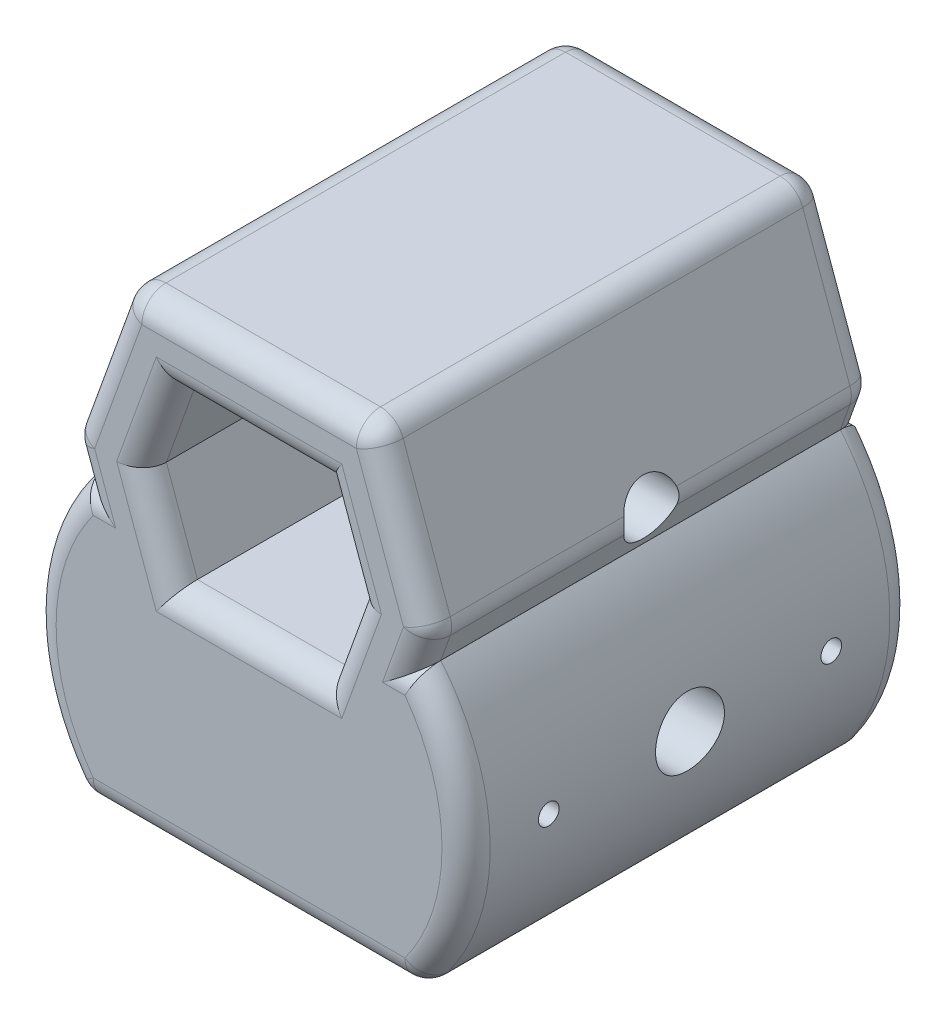
SolidWorks part; units mm, degrees
ref_plane "Front Plane" through (0, 0, 0) normal (0, 0, 1) x (1, 0, 0)
ref_plane "Top Plane" through (0, 0, 0) normal (0, 1, 0) x (1, 0, 0)
ref_plane "Right Plane" through (0, 0, 0) normal (1, 0, 0) x (0, 0, -1)
sketch "Sketch1" plane through (0, 0, 0) normal (0, 0, 1) x (1, 0, 0)
  circle A0 centre (0, 0) radius 31.5
  dimension "D1" = 63
extrude "Boss-Extrude1" add sketch "Sketch1" along normal blind 65
sketch "Sketch2" plane through (0, 0, 65) normal (0, 0, 1) x (1, 0, 0)
  line L1 (47.0231, -20) -> (-47.0231, -20)
  line L2 (47.0231, -20) -> (47.0231, 20)
  line L3 (47.0231, 20) -> (-47.0231, 20)
  line L4 (-47.0231, -20) -> (-47.0231, 20)
  line L5 (47.0231, -20) -> (-47.0231, 20) construction
  line L6 (47.0231, 20) -> (-47.0231, -20) construction
  point P0 (0, 0)
  dimension "D1" = 40
extrude "Cut-Extrude1" cut sketch "Sketch2" against normal through all both and the other way through all flip side to cut
sketch "Sketch3" plane through (0, 0, 65) normal (0, 0, 1) x (1, 0, 0)
  line L0 (0, 34.576) -> (0, 0) construction
  line L1 (0, 0) -> (50.0249, 0) construction
  line L8 (-11, 37.5) -> (11, 37.5)
  line L9 (11, 37.5) -> (15.5, 25)
  line L10 (15.5, 25) -> (11, 12.5)
  line L11 (11, 12.5) -> (-11, 12.5)
  line L12 (-15.5, 25) -> (-11, 12.5)
  line L13 (-11, 37.5) -> (-15.5, 25)
  line L16 (24.3362, 20) -> (-24.3362, 20) construction
  line L17 (-18.0283, 47.5) -> (18.0283, 47.5)
  line L18 (18.0283, 47.5) -> (26.1283, 25)
  line L19 (26.1283, 25) -> (18.0283, 2.5)
  line L20 (18.0283, 2.5) -> (-18.0283, 2.5)
  line L21 (-26.1283, 25) -> (-18.0283, 2.5)
  line L22 (-18.0283, 47.5) -> (-26.1283, 25)
  point P12 (0, 12.5)
  point P14 (0, 37.5)
  line M9 (24.3362, 20) -> (-24.3362, 20)
  dimension "D1" = 22
  dimension "D2" = 25
  dimension "D3" = 31
  dimension "D4" = 5
  dimension "D5" = 10
extrude "Boss-Extrude3" add sketch "Sketch3" against normal up to surface (65 mm away) contours L17 L18 L19 L20 L21 L22 up to face at (0, 0, 0)
extrude "Cut-Extrude2" cut sketch "Sketch3<4>" against normal through all both and the other way through all contours L8 L13 L12 L10 L9 M9 | L12 L11 L10 M9 region at (0, 28.3434, 65) region at (0, 16.3866, 65)
sketch "Sketch3<4>" plane through (0, 0, 65) normal (0, 0, 1) x (1, 0, 0) same geometry as "Sketch3"
sketch "Sketch5" plane through (0, 0, 0) normal (1, 0, 0) x (0, 0, -1)
  line L0 (0, 0) -> (-65, 0) construction
  line L1 (-65, 20) -> (-65, -20) construction
  line L2 (-32.5, 0) -> (-32.5, -30.2341) construction
  line L3 (0, 25) -> (-65, 25) construction
  circle A0 centre (-32.5, 0) radius 5
  circle A1 centre (-12, 0) radius 1.5
  circle A2 centre (-53, 0) radius 1.5
  circle A3 centre (-32.5, 25) radius 4
  dimension "D1" = 10
  dimension "D2" = 3
  dimension "D4" = 8
  dimension "D3" = 41
extrude "Cut-Extrude3" cut sketch "Sketch5" against normal through all both and the other way through all
fillet "Fillet1" radius 3.5 40 edges at (-13.25, 18.75, 65) (0, 12.5, 65) (13.25, 18.75, 65) (13.25, 31.25, 65) (0, 37.5, 65) (-13.25, 31.25, 65) (31.5, 0, 65) (0, -20, 65) (-31.5, 0, 65) (-24.3322, 20, 65) (-25.2283, 22.5, 65) (-22.0783, 36.25, 65) (0, 47.5, 65) (22.0783, 36.25, 65) (25.2283, 22.5, 65) (24.3322, 20, 65) (13.25, 31.25, 0) (13.25, 18.75, 0) (0, 12.5, 0) (-13.25, 18.75, 0) (-13.25, 31.25, 0) (0, 37.5, 0) (22.0783, 36.25, 0) (0, 47.5, 0) (-22.0783, 36.25, 0) (-25.2283, 22.5, 0) (-24.3322, 20, 0) (-31.5, 0, 0) (0, -20, 0) (31.5, 0, 0) (24.3322, 20, 0) (25.2283, 22.5, 0) (24.3362, -20, 32.5) (-24.3362, -20, 32.5) (26.1283, 25, 50.75) (26.1283, 25, 14.25) (-26.1283, 25, 14.25) (-26.1283, 25, 50.75) (-18.0283, 47.5, 32.5) (18.0283, 47.5, 32.5)
